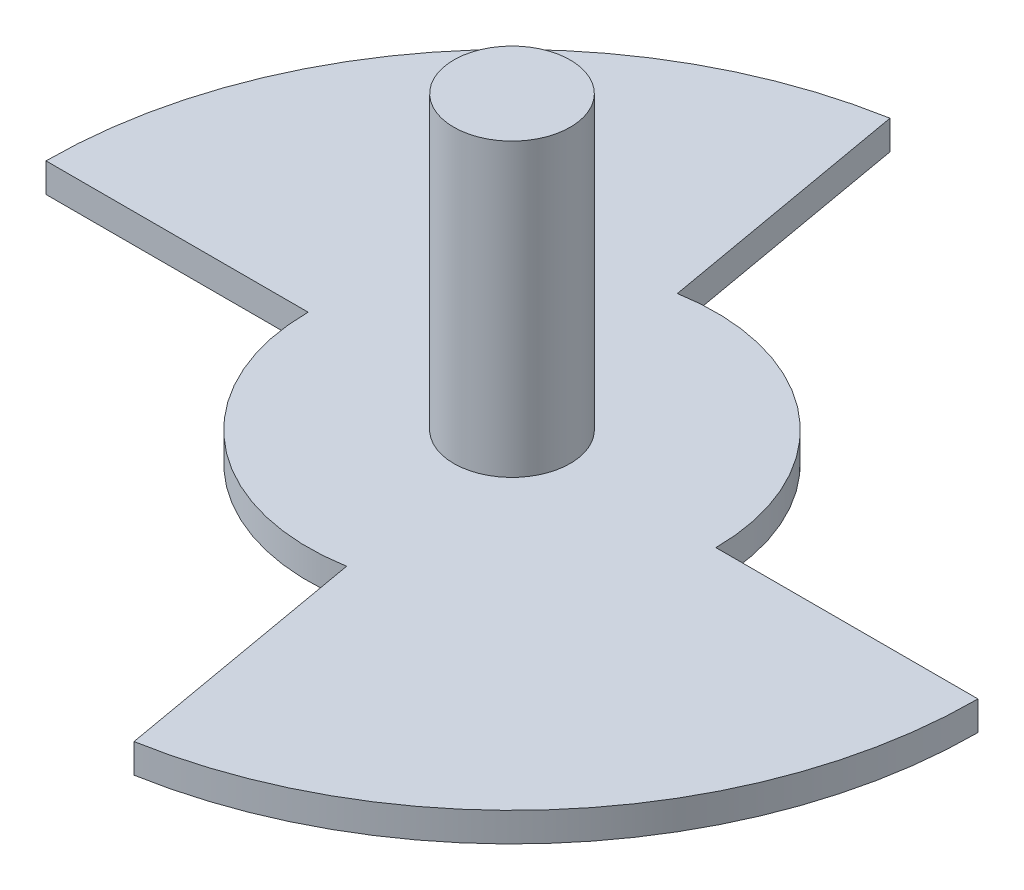
SolidWorks part; units mm, degrees
ref_plane "Alzado" through (0, 0, 0) normal (0, 0, 1) x (1, 0, 0)
ref_plane "Planta" through (0, 0, 0) normal (0, 1, 0) x (1, 0, 0)
ref_plane "Vista lateral" through (0, 0, 0) normal (1, 0, 0) x (0, 0, -1)
sketch "Croquis1" plane through (0, 0, 0) normal (0, 1, 0) x (1, 0, 0)
  line L0 (8, 0) -> (3.5, 0)
  line L1 (1.3892, -7.8785) -> (0.6078, -3.4468)
  line L2 (-0.6078, 3.4468) -> (-1.3892, 7.8785)
  line L3 (-3.5, 0) -> (-8, 0)
  arc A0 (1.3892, -7.8785) -> (8, 0) centre (0, 0) ccw
  arc A1 (-3.5, 0) -> (0.6078, -3.4468) centre (0, 0) ccw
  arc A2 (3.5, 0) -> (-0.6078, 3.4468) centre (0, 0) ccw
  arc A3 (-1.3892, 7.8785) -> (-8, 0) centre (0, 0) ccw
  dimension "D1" = 8
  dimension "D2" = 7
  dimension "D3" = 80
extrude "Saliente-Extruir1" add sketch "Croquis1" along normal blind 0.25 and the other way blind 0.25
sketch "Croquis2" plane through (0, 0.25, 0) normal (0, 1, 0) x (1, 0, 0)
  circle A0 centre (0, 0) radius 1
  dimension "D1" = 2
extrude "Saliente-Extruir2" add sketch "Croquis2" along normal blind 5
